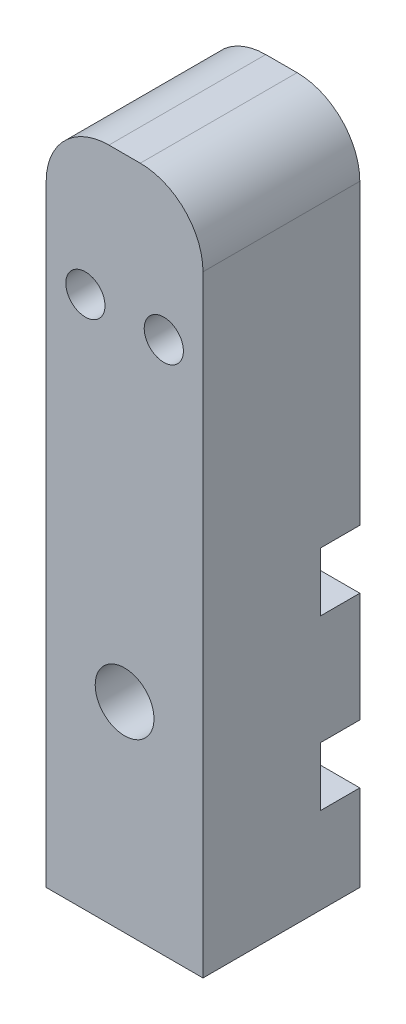
SolidWorks part; units mm, degrees
material "Plain Carbon Steel"
ref_plane "Front Plane" through (0, 0, 0) normal (0, 0, 1) x (1, 0, 0)
ref_plane "Top Plane" through (0, 0, 0) normal (0, 1, 0) x (1, 0, 0)
ref_plane "Right Plane" through (0, 0, 0) normal (1, 0, 0) x (0, 0, -1)
sketch "Sketch1" plane through (0, 0, 0) normal (0, 0, 1) x (1, 0, 0)
  line L1 (12.7, -54.61) -> (-12.7, -54.61)
  line L2 (12.7, -54.61) -> (12.7, 54.61)
  line L3 (12.7, 54.61) -> (-12.7, 54.61)
  line L4 (-12.7, -54.61) -> (-12.7, 54.61)
  line L5 (12.7, -54.61) -> (-12.7, 54.61) construction
  line L6 (12.7, 54.61) -> (-12.7, -54.61) construction
  point P0 (0, 0)
  dimension "D1" = 109.22
  dimension "D2" = 25.4
extrude "Boss-Extrude1" add sketch "Sketch1" against normal blind 25.4
fillet "Fillet1" radius 10.16 2 edges at (12.7, 54.61, -12.7) (-12.7, 54.61, -12.7)
sketch "Sketch2" plane through (0, -54.61, 0) normal (0, -1, 0) x (1, 0, 0)
  line L0 (-12.7, 0) -> (12.7, 0) construction
  line L1 (12.7, -25.4) -> (12.7, 0) construction
  circle A0 centre (0, -12.7) radius 3.175
  dimension "D1" = 6.35
  dimension "D2" = 12.7
  dimension "D3" = 12.7
extrude "Cut-Extrude1" cut sketch "Sketch2" against normal blind 17.78
sketch "Sketch3" plane through (0, 0, -25.4) normal (0, 0, -1) x (-1, 0, 0)
  line L0 (-2.54, 54.61) -> (2.54, 54.61) construction
  line L1 (12.7, 44.45) -> (12.7, -54.61) construction
  line L2 (0, -54.61) -> (0, 54.61) construction
  line L3 (12.7, -54.61) -> (-12.7, -54.61) construction
  circle A0 centre (0, 46.736) radius 4.7625
  circle A1 centre (6.35, 31.75) radius 3.175
  circle A2 centre (-6.35, 31.75) radius 3.175
  circle A3 centre (0, -22.225) radius 4.7625
  dimension "D1" = 9.525
  dimension "D3" = 6.35
  dimension "D4" = 6.35
  dimension "D5" = 22.86
  dimension "D6" = 9.525
  dimension "D7" = 32.385
  dimension "D2" = 7.874
extrude "Cut-Extrude2" cut sketch "Sketch3" against normal through all contours A2 | A1 | A3 L2 | L2 A3 region at (2.0213, -22.225, -25.4) region at (-2.0213, -22.225, -25.4) region at (-6.35, 31.75, -25.4) region at (6.35, 31.75, -25.4)
extrude "Cut-Extrude3" cut sketch "Sketch3<3>" against normal blind 16.51 contours L2 A0 | A0 L2 region at (2.0213, 46.736, -25.4) region at (-2.0213, 46.736, -25.4)
sketch "Sketch3<3>" plane through (0, 0, -25.4) normal (0, 0, -1) x (-1, 0, 0) same geometry as "Sketch3"
sketch "Sketch4" plane through (0, 0, -25.4) normal (0, 0, -1) x (-1, 0, 0)
  line L0 (12.7, 44.45) -> (12.7, -54.61) construction
  line L1 (12.7, -3.81) -> (-12.7, -3.81)
  line L2 (12.7, -3.81) -> (12.7, -13.335)
  line L3 (12.7, -13.335) -> (-12.7, -13.335)
  line L4 (-12.7, -3.81) -> (-12.7, -13.335)
  line L5 (-12.7, -54.61) -> (-12.7, 44.45) construction
  line L6 (0, -22.225) -> (12.7, -22.225) construction
  line L7 (12.7, -31.115) -> (-12.7, -31.115)
  line L8 (-12.7, -40.64) -> (-12.7, -31.115)
  line L9 (12.7, -40.64) -> (-12.7, -40.64)
  line L10 (12.7, -40.64) -> (12.7, -31.115)
  circle A1 centre (0, -22.225) radius 4.7625 construction
  dimension "D1" = 8.89
  dimension "D2" = 9.525
extrude "Cut-Extrude4" cut sketch "Sketch4" against normal blind 6.35
